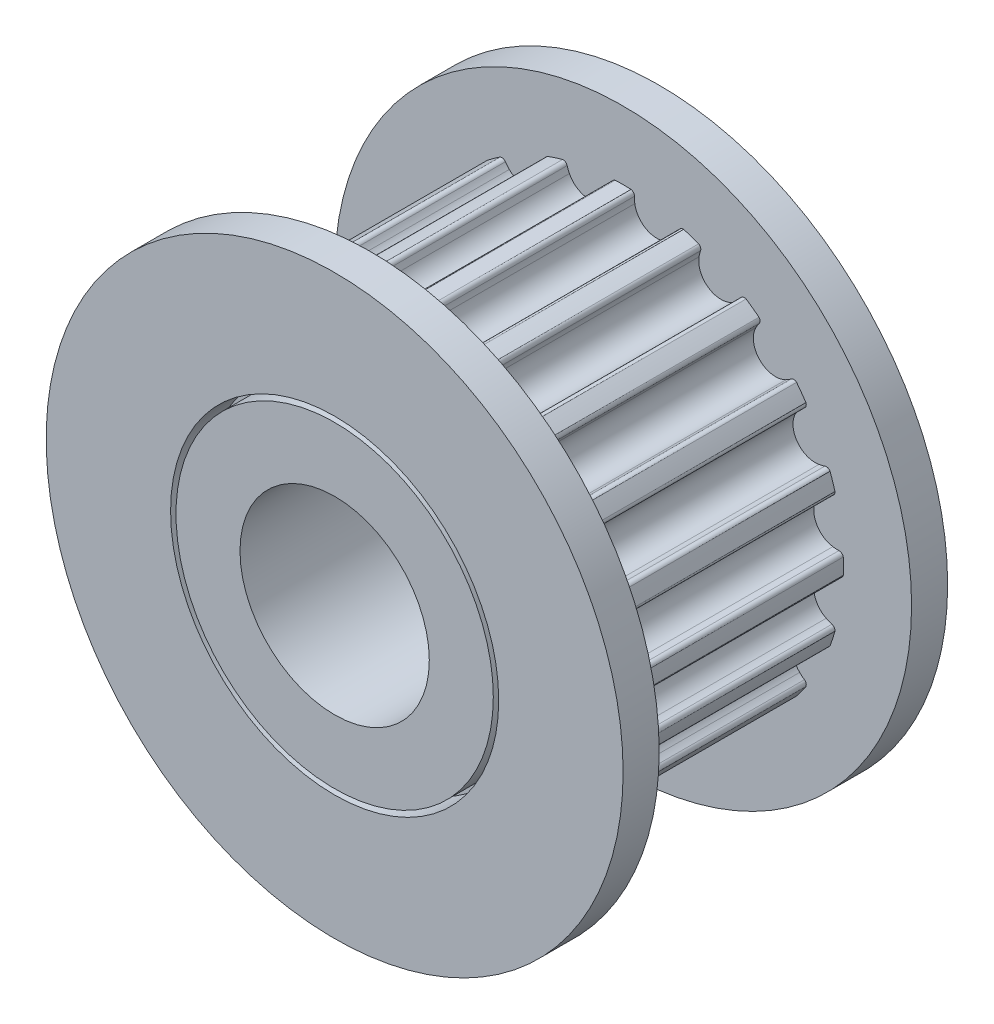
SolidWorks part; units mm, degrees
material "6063-T1"
ref_plane "Front Plane" through (0, 0, 0) normal (0, 0, 1) x (1, 0, 0)
ref_plane "Top Plane" through (0, 0, 0) normal (0, 1, 0) x (1, 0, 0)
ref_plane "Right Plane" through (0, 0, 0) normal (1, 0, 0) x (0, 0, -1)
sketch "Sketch5" plane through (0, 0, 0) normal (1, 0, 0) x (0, 0, -1)
  line L0 (0, 0) -> (0, 12.2271) construction
  line L2 (0.5, 8) -> (0.5, 6.11)
  line L3 (0.5, 6.11) -> (7.5, 6.11)
  line L4 (7.5, 6.11) -> (7.5, 8)
  line L5 (7.5, 8) -> (8.5, 8)
  line L6 (8.5, 8) -> (8.5, 2.625)
  line L8 (0, 0) -> (15.0467, 0) construction
  line L16 (-0.5, 2.625) -> (8.5, 2.625)
  line L18 (-0.5, 8) -> (0.5, 8)
  line L19 (-0.5, 8) -> (-0.5, 2.625)
  point P8 (0, 8)
  dimension "D1" = 12.22
  dimension "D2" = 7
  dimension "D3" = 9
  dimension "D4" = 1
  dimension "D5" = 16
  dimension "D6" = 5.25
revolve "Revolve1" add sketch "Sketch5" angle 360 about L8
sketch "Sketch6" plane through (0, 0, -0.5) normal (0, 0, 1) x (1, 0, 0)
  line L0 (0, 0) -> (0, 6.3662) construction
  line L1 (0, 0) -> (0.9959, 6.2878) construction
  line L2 (0, 0) -> (1.3887, 6.2129) construction
  line L3 (0, 6.1122) -> (0, 6.3662)
  line L4 (1.8888, 5.813) -> (1.9673, 6.0546)
  circle A1 centre (0, 0) radius 6.3662 construction
  arc A21 (0, 6.1122) -> (0.1975, 6.109) centre (0, 0) cw
  circle A22 centre (0, 0) radius 6.1122 construction
  circle A23 centre (0, 0) radius 5.3622 construction
  arc A24 (0.1975, 6.109) -> (0.3136, 5.9865) centre (0.1936, 5.9891) cw
  arc A25 (0.3136, 5.9865) -> (0.3242, 5.8165) centre (1.3333, 5.965) ccw
  arc A26 (0.3242, 5.8165) -> (1.4891, 5.632) centre (0.9355, 5.9064) ccw
  arc A27 (1.8888, 5.813) -> (1.7, 5.871) centre (0, 0) ccw
  arc A28 (1.5517, 5.7904) -> (1.4891, 5.632) centre (0.5752, 6.0851) cw
  arc A29 (1.7, 5.871) -> (1.5517, 5.7904) centre (1.6666, 5.7558) ccw
  arc A30 (0, 6.3662) -> (1.9676, 6.0545) centre (0, 0) cw
  circle M24 centre (0, 0) radius 6.11
  dimension "D1" = 12.7324
  dimension "D7" = 0.12
  dimension "D6" = 1.02
  dimension "D8" = 0.6179
  dimension "D2" = 0.254
  dimension "D3" = 0.75
  dimension "D4" = 9
  dimension "D5" = 3.6
extrude "Cut-Extrude1" cut sketch "Sketch6" against normal up to surface (7 mm away) contours L3 A30 L4 A27 A29 A24 A21 M24 | A29 A28 A26 A25 A24 M24 region at (0.972, 6.1372, -0.5) region at (0.905, 5.7137, -0.5) up to face at (6.11, 0, -7.5)
pattern_circular "CirPattern1" count 20 over 360 about axis through (0, 0, 0) along (0, 0, 1) of "Cut-Extrude1"
sketch "Sketch7" plane through (0, 0, 0.5) normal (0, 0, 1) x (1, 0, 0)
  circle A0 centre (0, 0) radius 8 construction
  circle A1 centre (0, 0) radius 2.625 construction
  circle A2 centre (0, 0) radius 8
  circle A3 centre (0, 0) radius 2.625
  circle A4 centre (0, 0) radius 4.4
  circle A5 centre (0, 0) radius 4.55
  circle M5 centre (0, 0) radius 8
  dimension "D1" = 8.8
  dimension "D2" = 0.15
extrude "Cut-Extrude2" cut sketch "Sketch7" against normal blind 1 contours A5 A4 | A5 M5 region at (-7.7737, 0, 0.5) region at (-4.4213, 0, 0.5)
extrude "Boss-Extrude1" add sketch "Sketch7<3>" against normal blind 1 separate body contours A5 M5 region at (-7.7737, 0, 0.5)
sketch "Sketch7<3>" plane through (0, 0, 0.5) normal (0, 0, 1) x (1, 0, 0) same geometry as "Sketch7"
equation "\"D1@Sketch6\"=2*20/pi"
